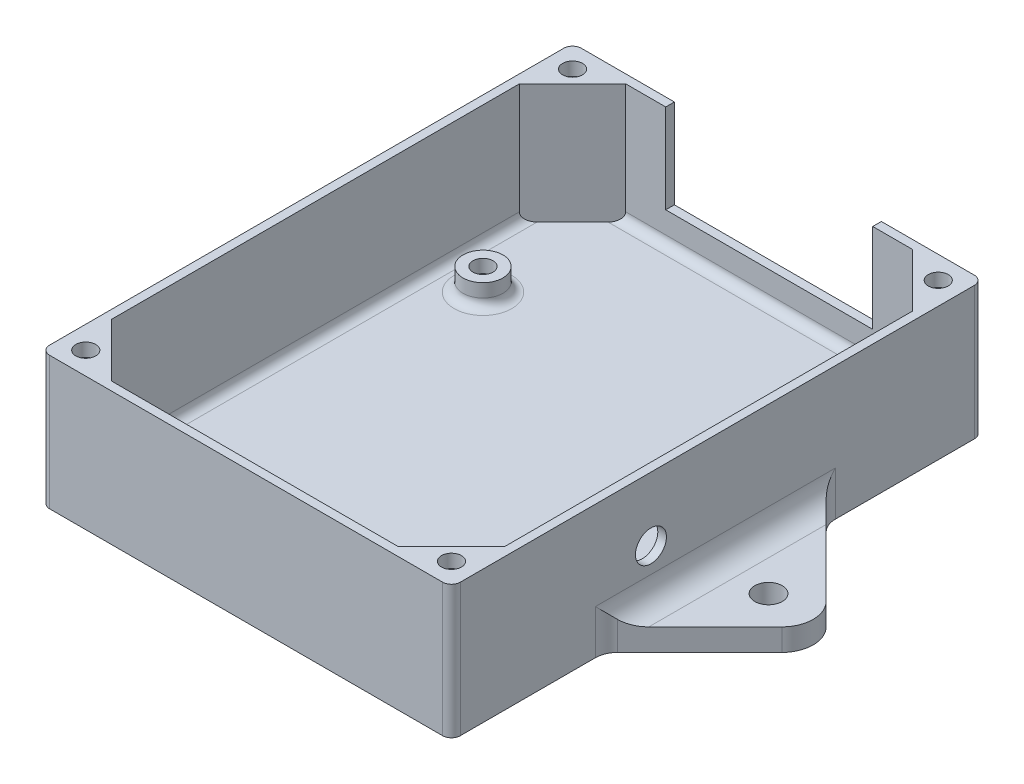
SolidWorks part; units mm, degrees
material "ABS"
ref_plane "Plan de face" through (0, 0, 0) normal (0, 0, 1) x (1, 0, 0)
ref_plane "Plan de dessus" through (0, 0, 0) normal (0, 1, 0) x (1, 0, 0)
ref_plane "Plan de droite" through (0, 0, 0) normal (1, 0, 0) x (0, 0, -1)
sketch "Repères_CI" plane through (0, 0, 0) normal (0, 1, 0) x (1, 0, 0)
  line L0 (-35.56, 52.58) -> (-39.37, 48.77) construction
  line L1 (-34.81, 28.71) -> (34.79, 28.71) construction
  line L2 (-34.81, 28.71) -> (-34.81, -48) construction
  line L3 (-34.81, -48) -> (34.79, -48) construction
  line L4 (34.79, 28.71) -> (34.79, -48) construction
  line L7 (-35.56, 52.58) -> (35.814, 52.58) construction
  line L8 (-39.37, 48.77) -> (-39.37, -48.77) construction
  line L9 (-35.56, -52.58) -> (35.56, -52.58) construction
  line L10 (39.37, 49.024) -> (39.37, -48.77) construction
  line L11 (-39.37, 52.58) -> (39.37, -52.58) construction
  line L12 (-39.37, -52.58) -> (39.37, 52.58) construction
  line L13 (35.814, 52.58) -> (39.37, 49.024) construction
  line L14 (39.37, -48.77) -> (35.56, -52.58) construction
  line L15 (-39.37, -48.77) -> (-35.56, -52.58) construction
  circle A0 centre (-34.81, 28.71) radius 1.5 construction
  circle A1 centre (34.79, 28.71) radius 1.5 construction
  circle A2 centre (34.79, -48) radius 1.5 construction
  circle A4 centre (-19.57, -48) radius 1.5 construction
  point P0 (0, 0)
  point P10 (0, 0)
  dimension "D1" = 3
  dimension "D12" = 15.24
  dimension "D2" = 69.6
  dimension "D3" = 76.71
  dimension "D4" = 78.74
  dimension "D5" = 105.16
  dimension "D6" = 4.58
  dimension "D7" = 4.58
sketch "Esquisse2" plane through (0, 0, 0) normal (0, 1, 0) x (1, 0, 0)
  line L0 (-46.32, 60.43) -> (-46.32, -59.53)
  line L5 (-39.37, 48.77) -> (-39.37, -48.77) construction
  line L6 (-44.37, 58.48) -> (44.37, 58.48)
  line L7 (-46.32, -59.53) -> (46.32, -59.53)
  line L8 (46.32, 60.43) -> (46.32, -59.53)
  line L9 (-44.37, 58.48) -> (-44.37, -57.58)
  line L10 (-44.37, -57.58) -> (44.37, -57.58)
  line L11 (44.37, 58.48) -> (44.37, -57.58)
  line L12 (39.37, 49.024) -> (39.37, -48.77) construction
  line L13 (-35.56, -52.58) -> (35.56, -52.58) construction
  line L14 (-35.56, 52.58) -> (35.814, 52.58) construction
  line L15 (-46.32, 60.43) -> (46.32, 60.43)
  dimension "D1" = 5
  dimension "D2" = 5
  dimension "D3" = 5
  dimension "D4" = 5.9
  dimension "D5" = 1.95
extrude "Base" add sketch "Esquisse2" against normal blind 3 contours L11 L6 L9 L10 | L15 L0 L7 L8 L6 L11 L10 L9 region at (0, 0, -58.9143) region at (0, 0, -0.45)
sketch "Esquisse3" plane through (0, 0, 0) normal (0, 1, 0) x (1, 0, 0)
  circle A0 centre (-34.81, 28.71) radius 4.5
  circle A1 centre (34.79, 28.71) radius 4.5
  circle A4 centre (-19.57, -48) radius 4.5
  circle A5 centre (34.79, -48) radius 4.5
  circle A6 centre (-34.81, 28.71) radius 1.5 construction
  point P8 (0, 0)
  point P9 (-34.81, -28.71)
  point P10 (-11.777, -40.5913)
  point P11 (-19.57, -48)
  point P17 (34.79, -48)
  point P19 (34.79, 28.71)
  dimension "D1" = 3
extrude "Support_PCB" add sketch "Esquisse3" along normal blind 5
sketch "Esquisse4" plane through (0, 5, 0) normal (0, 1, 0) x (1, 0, 0)
  circle A0 centre (-34.81, 28.71) radius 2.25
  circle A1 centre (34.79, 28.71) radius 2.25
  circle A2 centre (-19.57, -48) radius 2.25
  circle A3 centre (34.79, -48) radius 2.25
  circle A4 centre (-34.81, 28.71) radius 1.5
  circle A5 centre (-34.81, 28.71) radius 1.5 construction
  circle A6 centre (34.79, 28.71) radius 1.5
  circle A7 centre (34.79, 28.71) radius 1.5 construction
  circle A8 centre (-19.57, -48) radius 1.5
  circle A9 centre (34.79, -48) radius 1.5
  point P6 (0, 0)
  point P7 (34.79, -48)
  point P20 (0, 0)
  point P21 (-18.4159, -48.9479)
  point P22 (-19.57, -48)
  point P24 (34.79, -28.71)
  dimension "D1" = 4.5
extrude "Insert_M3_PCB" cut sketch "Esquisse4" against normal blind 3 contours A4 | A0 A4 | A6 | A1 A6 | A9 | A3 A9 | A8 | A2 A8 region at (-36.9964, 5, -28.71) region at (32.6036, 5, -28.71) region at (-21.7564, 5, 48) region at (32.6036, 5, 48) region at (-34.81, 5, -28.71) region at (34.79, 5, -28.71) region at (-19.57, 5, 48) region at (34.79, 5, 48)
extrude "Passage M3_PCB" cut sketch "Esquisse4<3>" against normal up to surface (5 mm away) contours A8 | A9 | A6 | A4 region at (-34.81, 5, -28.71) region at (34.79, 5, -28.71) region at (-19.57, 5, 48) region at (34.79, 5, 48) up to face at (34.79, 0, 43.5)
sketch "Esquisse4<3>" plane through (0, 5, 0) normal (0, 1, 0) x (1, 0, 0) same geometry as "Esquisse4"
extrude "Walls" add sketch "Esquisse2<4>" along normal blind 27 contours L15 L0 L7 L8 L6 L11 L10 L9 region at (0, 0, -58.9143)
sketch "Esquisse2<4>" plane through (0, 0, 0) normal (0, 1, 0) x (1, 0, 0) same geometry as "Esquisse2"
sketch "Esquisse5" plane through (0, 0, -60.43) normal (0, 0, -1) x (-1, 0, 0)
  line L0 (46.32, 27) -> (-46.32, 27) construction
  line L1 (-23.35, 27) -> (23.35, 27)
  line L2 (-23.35, 27) -> (-23.35, 6.9)
  line L3 (-23.35, 6.9) -> (23.35, 6.9)
  line L4 (23.35, 27) -> (23.35, 6.9)
  line L6 (44.37, 0) -> (-44.37, 0) construction
  point P6 (0, 6.9)
  dimension "D1" = 46.7
  dimension "D2" = 6.9
extrude "Ouverture_Conn_CMC" cut sketch "Esquisse5" against normal up to next
chamfer "Chanfrein1" distance 12 angle 45 4 edges at (-44.37, 13.5, -58.48) (44.37, 13.5, -58.48) (44.37, 13.5, 57.58) (-44.37, 13.5, 57.58)
fillet "Congé1" radius 2 12 edges at (0, 0, -58.48) (0, 0, 57.58) (44.37, 0, -0.45) (-44.37, 0, -0.45) (-46.32, 12, -60.43) (46.32, 12, -60.43) (46.32, 12, 59.53) (-46.32, 12, 59.53) (34.79, 0, -24.21) (-34.81, 0, -24.21) (34.79, 0, 43.5) (-19.57, 0, 43.5)
sketch "Esquisse6" plane through (0, 27, 0) normal (0, 1, 0) x (1, 0, 0)
  line L2 (-30.9558, 58.48) -> (-44.37, 45.0658) construction
  line L3 (-32.37, 58.48) -> (-23.35, 58.48) construction
  line L4 (-44.37, 46.48) -> (-44.37, -45.58) construction
  line L5 (-41.2488, 55.3588) -> (-41.2488, 60.43) construction
  line L6 (-44.32, 60.43) -> (-23.35, 60.43) construction
  line L7 (-41.2488, 55.3588) -> (-46.32, 55.3588) construction
  line L8 (-46.32, 58.43) -> (-46.32, -57.53) construction
  line L9 (-44.37, 46.48) -> (-32.37, 58.48) construction
  line L10 (-44.37, -44.1658) -> (-30.9558, -57.58) construction
  line L11 (-41.2488, 55.3588) -> (-37.6629, 51.7729) construction
  line L12 (-32.37, -57.58) -> (32.37, -57.58) construction
  line L13 (-32.37, -57.58) -> (-44.37, -45.58) construction
  line L14 (-41.2488, -54.4588) -> (-37.6629, -50.8729) construction
  line L15 (-41.2488, -54.4588) -> (-46.32, -54.4588) construction
  line L16 (-41.2488, -54.4588) -> (-41.2488, -59.53) construction
  line L17 (-44.32, -59.53) -> (44.32, -59.53) construction
  line L18 (0, -27.6425) -> (0, 27.6425) construction
  circle A0 centre (-41.2488, 55.3588) radius 2.25
  circle A1 centre (-41.2488, 55.3588) radius 1.6
  circle A8 centre (-41.2488, -54.4588) radius 1.6
  circle A9 centre (-41.2488, -54.4588) radius 2.25
  circle A10 centre (41.2488, 55.3588) radius 2.25
  circle A11 centre (41.2488, 55.3588) radius 1.6
  circle A12 centre (41.2488, -54.4588) radius 2.25
  circle A13 centre (41.2488, -54.4588) radius 1.6
  dimension "D1" = 4.5
  dimension "D2" = 3.2
  dimension "D3" = 1
  dimension "D4" = 1
extrude "Insert_M3_Box" cut sketch "Esquisse6" against normal blind 3 contours A1 | A0 A1 | A9 A8 | A8 | A13 | A12 A13 | A11 | A10 A11 region at (-43.4351, 27, -55.3588) region at (-41.2488, 27, -55.3588) region at (-41.2488, 27, 54.4588) region at (-43.4351, 27, 54.4588) region at (39.0624, 27, -55.3588) region at (41.2488, 27, -55.3588) region at (39.0624, 27, 54.4588) region at (41.2488, 27, 54.4588)
extrude "Passage_M3_Box" cut sketch "Esquisse6<3>" against normal blind 18 contours A1 | A13 | A8 | A11 region at (-41.2488, 27, -55.3588) region at (41.2488, 27, 54.4588)
sketch "Esquisse6<3>" plane through (0, 27, 0) normal (0, 1, 0) x (1, 0, 0) same geometry as "Esquisse6"
sketch "Esquisse10" plane through (0, -3, 0) normal (0, -1, 0) x (1, 0, 0)
  line L0 (46.32, 25) -> (66.32, 5)
  line L1 (46.32, -58.43) -> (46.32, 57.53) construction
  line L2 (46.32, -25) -> (66.32, -5)
  line L3 (46.32, 25) -> (46.32, -25)
  line L8 (0, -57.838) -> (0, 57.838) construction
  line L9 (-46.32, 25) -> (-66.32, 5)
  line L10 (-46.32, -25) -> (-66.32, -5)
  line L11 (-46.32, 25) -> (-46.32, -25)
  arc A0 (66.32, 5) -> (66.32, -5) centre (61.32, 0) cw
  circle A2 centre (58.32, 0) radius 3.1
  circle A3 centre (-58.32, 0) radius 3.1
  arc A4 (-66.32, 5) -> (-66.32, -5) centre (-61.32, 0) ccw
  point P10 (46.32, 0)
  dimension "D5" = 6.2
  dimension "D1" = 50
  dimension "D2" = 25
  dimension "D3" = 20
  dimension "D4" = 10
  dimension "D6" = 12
extrude "Boss.-Extru.2" add sketch "Esquisse10" against normal blind 5
fillet "Congé4" radius 5 6 edges at (-46.32, -0.5, -25) (-46.32, 2, 0) (-46.32, -0.5, 25) (46.32, -0.5, -25) (46.32, -0.5, 25) (46.32, 2, 0)
sketch "Esquisse11" plane through (46.32, 0, 0) normal (1, 0, 0) x (0, 0, -1)
  line L0 (-59.53, -3) -> (-59.53, 27) construction
  line L1 (-49.024, 6.6) -> (48.77, 6.6) construction
  circle A0 centre (-14.53, 12.6) radius 3.5
  dimension "D3" = 7
  dimension "D1" = 45
  dimension "D2" = 6
extrude "Passage_MAP" cut sketch "Esquisse11" against normal up to next
equation "\"D2@Esquisse10\"=\"D1@Esquisse10\"/2"
